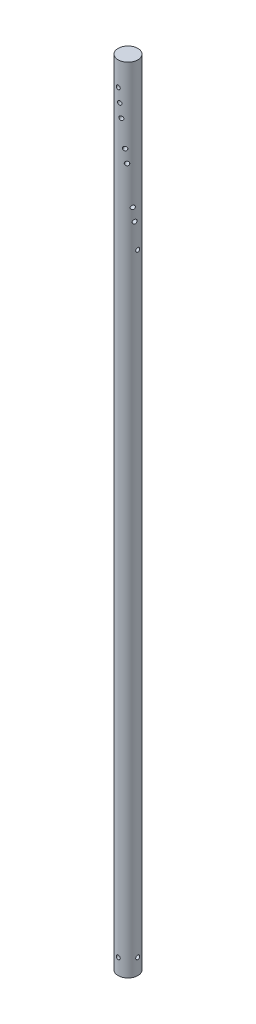
SolidWorks part; units mm, degrees
material "AISI 316 Annealed Stainless Steel Bar (SS)"
ref_plane "Front" through (0, 0, 0) normal (0, 0, 1) x (1, 0, 0)
ref_plane "Top" through (0, 0, 0) normal (0, 1, 0) x (1, 0, 0)
ref_plane "Right" through (0, 0, 0) normal (1, 0, 0) x (0, 0, -1)
sketch "Sketch1" plane through (0, 0, 0) normal (0, 1, 0) x (1, 0, 0)
  circle A1 centre (0, 0) radius 12.5
  dimension "D1" = 25
extrude "Boss-Extrude1" add sketch "Sketch1" along normal blind 1000
sketch "Sketch2" plane through (0, 1000, 0) normal (0, 1, 0) x (1, 0, 0)
  line L0 (-9.5, 8.124) -> (9.5, 8.124)
  arc A0 (9.5, 8.124) -> (-9.5, 8.124) centre (0, 0) ccw
  dimension "D1" = 25
  dimension "D2" = 19
extrude "Cut-Extrude1" [suppressed] cut sketch "Sketch2" against normal blind 300
sketch3d "3DSketch1"
  circle A0 centre (0, 970, 0) radius 12.5
  point P2 (0, 957.5, 0)
  dimension "D1" = 25
curve "Helix/Spiral1" pitch 710 height 177.5 turns 0.25
hole_wizard "#8 (0.199) Diameter Hole2" positions "3DSketch5" profile "Sketch10" hole size "#8" standard "ANSI Inch" end condition through all
sketch3d "3DSketch5"
  spline S0 degree 3 poles (0, 970, -12.5) (-0.595, 964.6213, -12.5) (-1.785, 953.8636, -12.4149) (-3.5336, 937.7273, -12.0345) (-5.2104, 921.5909, -11.4091) (-6.781, 905.4545, -10.5515) (-8.2136, 889.3182, -9.479) (-9.479, 873.1818, -8.2136) (-10.5515, 857.0455, -6.781) (-11.4091, 840.9091, -5.2104) (-12.0345, 824.7727, -3.5336) (-12.4149, 808.6364, -1.785) (-12.5, 797.8787, -0.595) (-12.5, 792.5, 0) knots 0 0 0 0 0.090909 0.181818 0.272727 0.363636 0.454545 0.545455 0.636364 0.727273 0.818182 0.909091 1 1 1 1 construction
  point P63 (-1.7833, 953.8233, -12.3721)
  point P65 (-3.5194, 937.7487, -11.9943)
  point P67 (-6.759, 905.4439, -10.515)
  point P69 (-8.1859, 889.3169, -9.4468)
  point P77 (-11.37, 840.9175, -5.1935)
  point P79 (-11.9937, 824.7727, -3.5217)
  point P96 (0, 970, -12.5)
  point P111 (-11.3704, 840.9091, -5.1927)
  point P113 (-12.5, 792.5001, 0)
  point P118 (-11.37, 840.9175, -5.1935)
sketch "Sketch10" plane through (-1.7833, 953.8233, -12.3721) normal (0, 1, 0) x (-0.9898, 0, 0.1427)
  line L0 (0, 0) -> (0, 26.6555)
  line L1 (0, 26.6555) -> (2.5273, 26.6555)
  line L2 (2.5273, 26.6555) -> (2.5273, 0)
  line L5 (2.5273, 0) -> (0, 0)
  line L11 (0, -6.35) -> (0, 107.95) construction
  dimension "Thru Hole Dia." = 5.0546
  dimension "Thru Hole Depth" = 26.6555
hole_wizard "#8 (0.199) Diameter Hole3" positions "3DSketch6" profile "Sketch11" hole size "#8" standard "ANSI Inch" end condition through all
sketch3d "3DSketch6"
  point P0 (-12.5, 20, 0)
  point P2 (0, 20, -12.5)
  dimension "D1" = 20
  dimension "D2" = 20
sketch "Sketch11" plane through (-12.5, 20, 0) normal (0, 1, 0) x (0, 0, 1)
  line L0 (0, 0) -> (0, 25)
  line L1 (0, 25) -> (2.5273, 25)
  line L2 (2.5273, 25) -> (2.5273, 0)
  line L5 (2.5273, 0) -> (0, 0)
  line L11 (0, -6.35) -> (0, 107.95) construction
  dimension "Thru Hole Dia." = 5.0546
  dimension "Thru Hole Depth" = 25
sketch3d "3DSketch7" plane through (0, 0, 0) normal (0, 0, 1) x (1, 0, 0)
